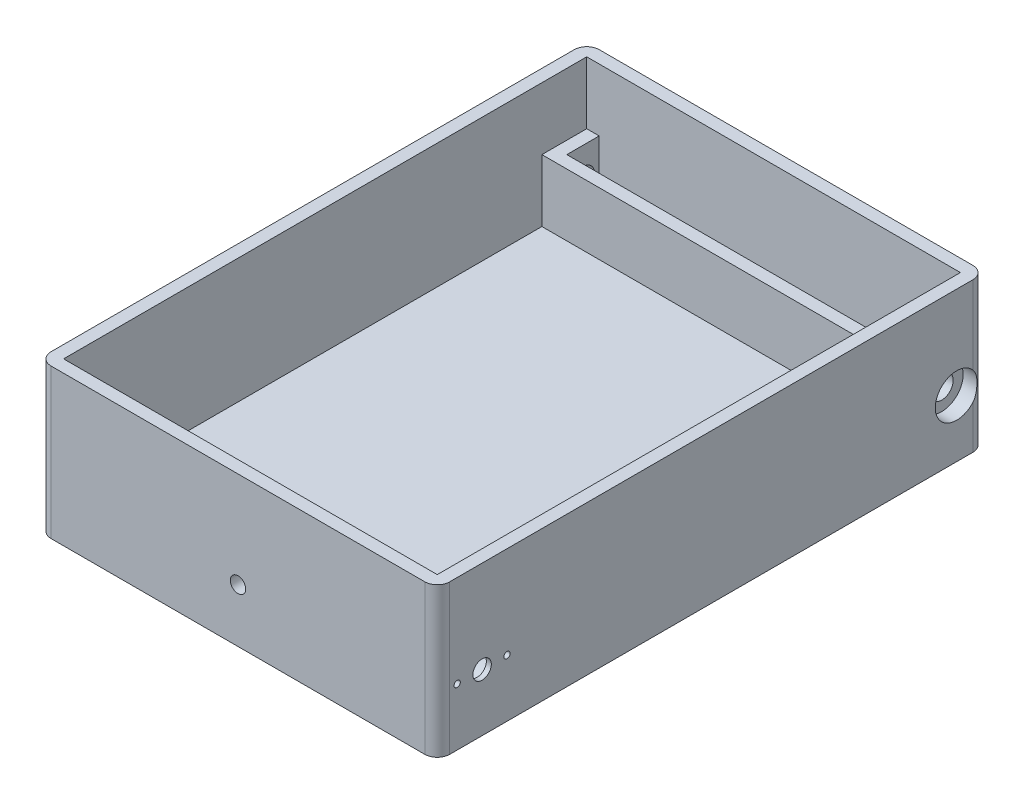
SolidWorks part; units mm, degrees
ref_plane "Front Plane" through (0, 0, 0) normal (0, 0, 1) x (1, 0, 0)
ref_plane "Top Plane" through (0, 0, 0) normal (0, 1, 0) x (1, 0, 0)
ref_plane "Right Plane" through (0, 0, 0) normal (1, 0, 0) x (0, 0, -1)
sketch "Main Body" plane through (0, 0, 0) normal (0, 1, 0) x (1, 0, 0)
  line L0 (-75, 110) -> (75, 110)
  line L1 (-75, -105) -> (75, -105)
  line L2 (-75, -105) -> (-75, 105)
  line L3 (-75, 105) -> (75, 105)
  line L4 (75, -105) -> (75, 105)
  line L5 (-75, -105) -> (75, 105) construction
  line L6 (-75, 105) -> (75, -105) construction
  line L7 (80, -105) -> (80, 105)
  line L8 (-75, -110) -> (75, -110)
  line L9 (-80, -105) -> (-80, 105)
  line L10 (-80, -110) -> (80, -110) construction
  line L11 (-80, -110) -> (-80, 110) construction
  line L12 (80, -110) -> (80, 110) construction
  line L13 (-80, 110) -> (80, 110) construction
  arc A0 (-75, -110) -> (-80, -105) centre (-75, -105) cw
  arc A1 (80, -105) -> (75, -110) centre (75, -105) cw
  arc A2 (75, 110) -> (80, 105) centre (75, 105) cw
  arc A3 (-75, 110) -> (-80, 105) centre (-75, 105) ccw
  point P0 (0, 0)
  dimension "D4" = 5
  dimension "D1" = 75
  dimension "D2" = 210
  dimension "D3" = 5
extrude "Boss-Extrude1" add sketch "Main Body" along normal blind 10 contours L1 L4 L3 L2 | L9 L8 L7 L0 L4 L1 L2 L3 region at (0, 0, -107.2797) region at (0, 0, 0)
extrude "Boss-Extrude3" add sketch "Main Body<4>" along normal blind 50 from surface starting at face at (0, 10, 0)
sketch "Main Body<4>" plane through (0, 0, 0) normal (0, 1, 0) x (1, 0, 0) same geometry as "Main Body"
sketch "Sketch1" plane through (75, 0, 0) normal (-1, 0, 0) x (0, 0, 1)
  line L0 (105, 60) -> (105, 10) construction
  line L1 (-105, 10) -> (105, 10) construction
  line L2 (79, 17.5) -> (105, 17.5)
  line L3 (79, 10) -> (105, 10)
  line L4 (79, 10) -> (79, 36)
  line L5 (79, 36) -> (105, 36)
  line L6 (105, 10) -> (105, 36)
  line L7 (79, 10) -> (105, 36) construction
  line L8 (79, 36) -> (105, 10) construction
  circle A0 centre (92, 23) radius 13
  line M2 (-105, 10) -> (105, 10)
  line M3 (105, 10) -> (105, 60)
  dimension "D1" = 26
  dimension "D2" = 7.5
extrude "Boss-Extrude4" add sketch "Sketch1" along normal up to surface (150 mm away) contours A0 L4 M2 | A0 L3 M3 region at (75, 12.5201, 82.0674) region at (75, 12.5201, 101.9326) up to face at (-75, 35, 0)
sketch "Sketch2" plane through (0, 0, 0) normal (1, 0, 0) x (0, 0, -1)
  line L0 (-105, 60) -> (-105, 17.5) construction
  line L1 (-105, 10) -> (-79, 10)
  line L2 (-105, 10) -> (-105, 17.5)
  line L3 (-105, 17.5) -> (-79, 17.5)
  line L4 (-79, 10) -> (-79, 17.5)
  line L5 (105, 10) -> (-79, 10) construction
  line L6 (-79, 10) -> (-79, 17.5) construction
  line L7 (-79, 17.5) -> (-80.2208, 17.5) construction
extrude "Cut-Extrude1" cut sketch "Sketch2" against normal mid plane 12
sketch "Sketch3" plane through (0, 10, 0) normal (0, 1, 0) x (1, 0, 0)
  line L0 (75, -105) -> (-75, -105) construction
  line L1 (-4, -79) -> (-11, -79)
  line L2 (-4, -79) -> (-4, -105)
  line L3 (-4, -105) -> (-11, -105)
  line L4 (-11, -79) -> (-11, -105)
  line L5 (0, 0) -> (0, -105) construction
  line L6 (-75, -79) -> (-6, -79) construction
  line L7 (11, -79) -> (11, -105)
  line L8 (4, -105) -> (11, -105)
  line L9 (4, -79) -> (4, -105)
  line L10 (4, -79) -> (11, -79)
  line L11 (-6, -103.7792) -> (-6, -92) construction
  point P10 (-2.3513, -79)
  dimension "D1" = 5
  dimension "D2" = 4
extrude "Boss-Extrude5" add sketch "Sketch3" along normal blind 20
sketch "Sketch4" plane through (0, 10, 0) normal (0, 1, 0) x (1, 0, 0)
  line L0 (-75, -105) -> (-75, 105) construction
  line L1 (-75, 92) -> (75, 92)
  line L2 (-75, 92) -> (-75, 87)
  line L3 (-75, 87) -> (75, 87)
  line L4 (75, 92) -> (75, 87)
  line L5 (75, 105) -> (75, -105) construction
  line L6 (-75, 105) -> (75, 105) construction
  dimension "D1" = 18
  dimension "D2" = 5
extrude "Boss-Extrude6" add sketch "Sketch4" along normal blind 25
sketch "Sketch5" plane through (80, 0, 0) normal (1, 0, 0) x (0, 0, -1)
  circle A0 centre (-92, 23) radius 3.5 construction
  circle A1 centre (-92, 23) radius 3.5
  circle A2 centre (-92, 23) radius 3.7
  dimension "D1" = 0.2
extrude "Cut-Extrude4" cut sketch "Sketch5" against normal up to next contours A1 | A2 A1 region at (80, 23, 92) region at (80, 23, 95.5953)
sketch "Sketch6" plane through (-75, 0, 0) normal (1, 0, 0) x (0, 0, -1)
  circle A0 centre (-92, 23) radius 13
  dimension "D1" = 26
extrude "Cut-Extrude5" cut sketch "Sketch6" against normal offset from surface (3 mm away) 2 up to face at (-80, 30, 0)
mirror "Mirror1" about plane through (0, 0, 0) normal (1, 0, 0) of "Cut-Extrude4"
sketch "Sketch8" plane through (75, 0, 0) normal (-1, 0, 0) x (0, 0, 1)
  circle A0 centre (92, 23) radius 13
  dimension "D1" = 26
extrude "Cut-Extrude6" cut sketch "Sketch8" against normal offset from surface (3 mm away) 2 up to face at (80, 23, 88.3)
sketch "Sketch10" plane through (80, 0, 0) normal (1, 0, 0) x (0, 0, -1)
  circle A1 centre (-82, 23) radius 1.25
  circle A2 centre (-82, 23) radius 1.25
  circle A3 centre (-102, 23) radius 1.25
  circle A4 centre (-102, 23) radius 1.25
  circle A5 centre (-92, 23) radius 12.5
  circle A6 centre (-92, 23) radius 12.5
  dimension "D1" = 0
  dimension "D2" = 0
  dimension "D3" = 0
extrude "Cut-Extrude7" cut sketch "Sketch10" against normal up to next contours A2 | A4 region at (80, 23, 82) region at (80, 23, 102)
mirror "Mirror3" about plane through (0, 0, 0) normal (1, 0, 0) of "Cut-Extrude7"
sketch "Sketch11" plane through (80, 0, 0) normal (1, 0, 0) x (0, 0, -1)
  circle A0 centre (98.5, 23) radius 4.5 construction
  circle A1 centre (98.5, 23) radius 4.5
  circle A3 centre (98.5, 23) radius 4.6
  dimension "D1" = 0.1
extrude "Cut-Extrude10" cut sketch "Sketch11" against normal through all contours A1 | A3 A1 region at (80, 23, -98.5) region at (80, 23, -93.913)
sketch "Sketch12" plane through (-75, 0, 0) normal (1, 0, 0) x (0, 0, -1)
  line L0 (92, 10) -> (105, 10) construction
  line L1 (92, 35) -> (105, 35)
  line L2 (92, 35) -> (92, 10)
  line L3 (92, 10) -> (105, 10)
  line L4 (105, 35) -> (105, 10)
  line L6 (92, 35) -> (92, 10) construction
  line L7 (92, 35) -> (87, 35) construction
  circle A2 centre (98.5, 23) radius 4.6 construction
  circle A3 centre (98.5, 23) radius 4.6
extrude "Boss-Extrude7" add sketch "Sketch12" along normal blind 5
sketch "Sketch13" plane through (-80, 0, 0) normal (-1, 0, 0) x (0, 0, 1)
  circle A0 centre (-98.5, 23) radius 8.6
  circle A2 centre (-98.5, 23) radius 4.6 construction
  dimension "D1" = 17.2
extrude "Cut-Extrude11" cut sketch "Sketch13" against normal blind 6
mirror "Mirror4" about plane through (0, 0, 0) normal (1, 0, 0) of "Boss-Extrude7", "Cut-Extrude11"
sketch "Sketch14" plane through (0, 10, 0) normal (0, 1, 0) x (1, 0, 0)
  line L0 (-4, -105) -> (-4, -79) construction
  line L1 (-4, -95) -> (4, -95)
  line L2 (-4, -95) -> (-4, -105)
  line L3 (-4, -105) -> (4, -105)
  line L4 (4, -95) -> (4, -105)
  dimension "D1" = 10
extrude "Boss-Extrude9" add sketch "Sketch14" along normal blind 5
sketch "Sketch15" plane through (0, 0, 110) normal (0, 0, 1) x (1, 0, 0)
  arc A0 (-3, 21.5) -> (3, 21.5) centre (0, 21.5) ccw construction
  arc A1 (-3, 21.5) -> (3, 21.5) centre (0, 21.5) ccw
  arc A2 (3, 21.5) -> (-3, 21.5) centre (0, 21.5) ccw construction
  arc A3 (3, 21.5) -> (-3, 21.5) centre (0, 21.5) ccw
  arc A4 (3.1, 21.5) -> (-3.1, 21.5) centre (0, 21.5) ccw
  arc A5 (-3.1, 21.5) -> (3.1, 21.5) centre (0, 21.5) ccw
  dimension "D1" = 0.1
extrude "Cut-Extrude12" cut sketch "Sketch15" against normal up to next contours A1 A3 | A4 A5 A3 A1 region at (0, 21.5, 110) region at (0, 18.4877, 110)
